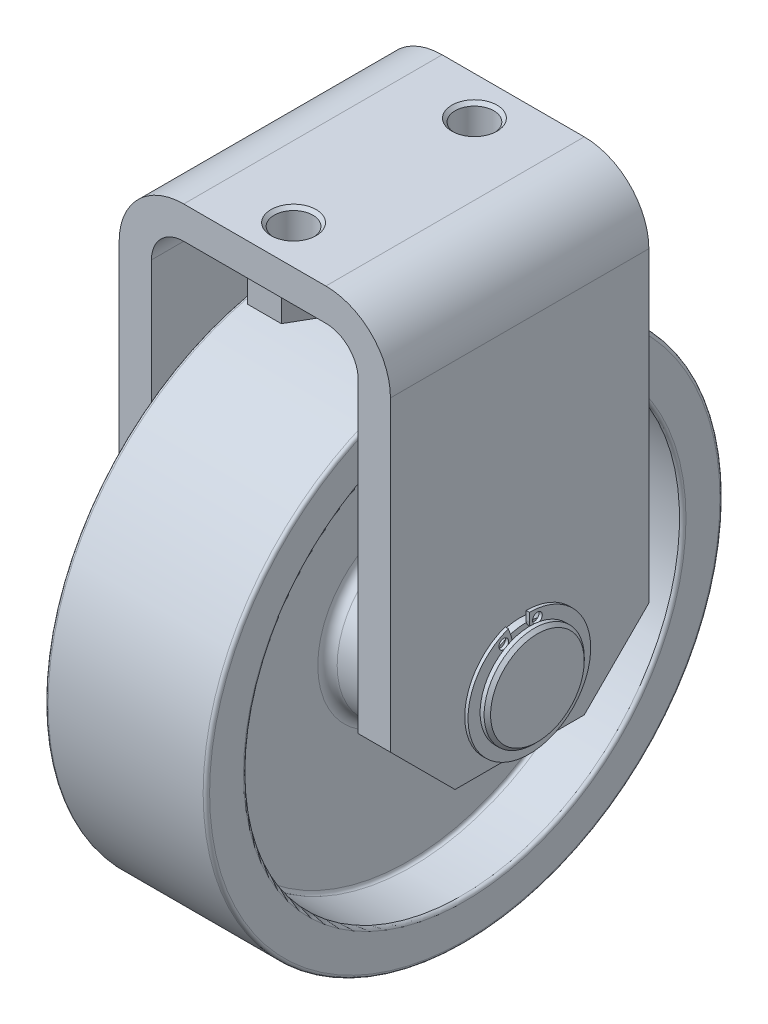
SolidWorks part; units mm, degrees
ref_plane "Front Plane" through (0, 0, 0) normal (0, 0, 1) x (1, 0, 0)
ref_plane "Top Plane" through (0, 0, 0) normal (0, 1, 0) x (1, 0, 0)
ref_plane "Right Plane" through (0, 0, 0) normal (1, 0, 0) x (0, 0, -1)
sketch "Sketch1" plane through (0, 0, 0) normal (0, 0, 1) x (1, 0, 0)
  line L0 (-43.3817, 0) -> (51.6188, 0) construction
  line L1 (55, 0) -> (-55, 0) construction
  line L2 (24, 16) -> (-24, 16)
  line L3 (0, -55) -> (0, 55) construction
  line L4 (-24, 16) -> (-24, 24)
  line L5 (-23, 25) -> (-10.5, 25)
  line L6 (-7.5, 28) -> (-7.5, 66.5)
  line L7 (-8.5, 67.5) -> (-24, 67.5)
  line L8 (-25, 68.5) -> (-25, 79)
  line L9 (-24, 80) -> (24, 80)
  line L10 (0, 80) -> (0, 16) construction
  line L11 (24, 16) -> (24, 24)
  line L12 (23, 25) -> (10.5, 25)
  line L13 (7.5, 28) -> (7.5, 66.5)
  line L14 (8.5, 67.5) -> (24, 67.5)
  line L15 (25, 68.5) -> (25, 79)
  arc A0 (-24, 24) -> (-23, 25) centre (-23, 24) cw
  arc A1 (-7.5, 66.5) -> (-8.5, 67.5) centre (-8.5, 66.5) ccw
  arc A2 (-24, 67.5) -> (-25, 68.5) centre (-24, 68.5) cw
  arc A3 (-25, 79) -> (-24, 80) centre (-24, 79) cw
  arc A4 (-10.5, 25) -> (-7.5, 28) centre (-10.5, 28) ccw
  arc A5 (24, 24) -> (23, 25) centre (23, 24) ccw
  arc A6 (10.5, 25) -> (7.5, 28) centre (10.5, 28) cw
  arc A7 (7.5, 66.5) -> (8.5, 67.5) centre (8.5, 66.5) cw
  arc A8 (24, 67.5) -> (25, 68.5) centre (24, 68.5) ccw
  arc A9 (25, 79) -> (24, 80) centre (24, 79) ccw
  point P22 (-25, 80)
  dimension "D8" = 1
  dimension "D9" = 3
  dimension "D1" = 50
  dimension "D2" = 135
  dimension "D3" = 160
  dimension "D4" = 25
  dimension "D5" = 7.5
  dimension "D6" = 24
  dimension "D7" = 16
revolve "Revolve1" add sketch "Sketch1" angle 360 about L0
sketch "Sketch2" plane through (0, 0, 0) normal (0, 0, 1) x (1, 0, 0)
  line L0 (-42, -20) -> (-42, 95)
  line L1 (-22, 115) -> (22, 115)
  line L2 (42, 95) -> (42, -20)
  line L3 (0, -88) -> (0, 88) construction
  line L4 (27.5, 0) -> (-27.5, 0) construction
  arc A0 (22, 115) -> (42, 95) centre (22, 95) cw
  arc A1 (-42, 95) -> (-22, 115) centre (-22, 95) cw
  point P2 (0, 115)
  point P11 (42, 115)
  point P14 (-42, 115)
  dimension "D4" = 20
  dimension "D1" = 135
  dimension "D2" = 84
  dimension "D3" = 115
extrude "Extrude-Thin1" add sketch "Sketch2" along normal mid plane 80 separate body thin
sketch "Sketch3" plane through (42, 0, 0) normal (1, 0, 0) x (0, 0, -1)
  circle A0 centre (0, 0) radius 16
  circle A1 centre (0, 0) radius 16 construction
extrude "Cut-Extrude1" cut sketch "Sketch3" against normal up to surface (84 mm away) up to face at (-42, 37.5, 0)
sketch "Sketch4" plane through (0, 0, 0) normal (1, 0, 0) x (0, 0, -1)
  circle A2 centre (0, 0) radius 15.5
  circle A3 centre (0, 0) radius 15.5
  dimension "D1" = 0.5
extrude "Boss-Extrude1" add sketch "Sketch4" along normal mid plane 95 separate body
chamfer "Chamfer1" distance 1 angle 45 2 edges at (-47.5, 0, -15.5) (47.5, 0, -15.5)
sketch "Sketch5" plane through (0, 0, 0) normal (0, 0, 1) x (1, 0, 0)
  line L0 (46.5, 15.5) -> (-46.5, 15.5) construction
  line L1 (-45.25, 15.5) -> (-43.75, 15.5)
  line L2 (-45.25, 15.5) -> (-45.25, 13.5)
  line L3 (-45.25, 13.5) -> (-43.75, 13.5)
  line L4 (-43.75, 15.5) -> (-43.75, 13.5)
  line L5 (-45.25, 15.5) -> (-43.75, 13.5) construction
  line L6 (-45.25, 13.5) -> (-43.75, 15.5) construction
  line L7 (-47.5, 14.5) -> (-47.5, -14.5) construction
  line L8 (0, 129.3642) -> (0, -93.634) construction
  line L9 (0, -88) -> (0, 88) construction
  line L10 (43.75, 15.5) -> (43.75, 13.5)
  line L11 (45.25, 15.5) -> (43.75, 15.5)
  line L12 (45.25, 15.5) -> (45.25, 13.5)
  line L13 (45.25, 13.5) -> (43.75, 13.5)
  point P4 (-44.5, 14.5)
  dimension "D1" = 3
  dimension "D2" = 1.5
  dimension "D3" = 2
revolve "Cut-Revolve1" cut sketch "Sketch5" angle 360
sketch "Sketch6" plane through (0, 0, 0) normal (0, 0, 1) x (1, 0, 0)
  line L0 (-43.75, 13.5) -> (-45.25, 13.5) construction
  line L1 (-45, 14) -> (-44, 14)
  line L2 (-45, 14) -> (-45, 19)
  line L3 (-45, 19) -> (-44, 19)
  line L4 (-44, 14) -> (-44, 19)
  line L5 (-45, 14) -> (-44, 19) construction
  line L6 (-45, 19) -> (-44, 14) construction
  line L7 (-45.25, -15.5) -> (-45.25, 15.5) construction
  point P4 (-44.5, 16.5)
  dimension "D1" = 5
  dimension "D2" = 0.5
  dimension "D3" = 1
  dimension "D4" = 0.25
revolve "Revolve2" add sketch "Sketch6" angle 340
sketch "Sketch7" plane through (-45, 0, 0) normal (-1, 0, 0) x (0, 0, 1)
  line L0 (0, 19) -> (0, 14) construction
  line L1 (6.4984, 17.8542) -> (4.7883, 13.1557) construction
  circle A0 centre (7.9274, 14.4709) radius 1.5
  circle A1 centre (-2.5, 16.3095) radius 1.5
  arc A4 (0, 16.5) -> (5.6433, 15.5049) centre (0, 0) ccw
  arc A5 (0, 16.5) -> (5.6433, 15.5049) centre (0, 0) ccw construction
  dimension "D1" = 2.5
  dimension "D3" = 3
  dimension "D2" = 2.5
  dimension "D4" = 2.5
extrude "Cut-Extrude2" cut sketch "Sketch7" against normal up to surface (1 mm away) up to face at (-44, -0.1234, -0.0218)
fillet "Fillet1" radius 2.5 2 edges at (-44.5, 13.1557, 4.7883) (-44.5, 14, 0)
mirror "Mirror3" about plane through (0, 0, 0) normal (1, 0, 0) of bodies 107
sketch "Sketch8" plane through (0, 105, 0) normal (0, -1, 0) x (1, 0, 0)
  line L1 (5.1962, -37) -> (10.3923, -28)
  line L2 (10.3923, -28) -> (5.1962, -19)
  line L3 (5.1962, -19) -> (-5.1962, -19)
  line L4 (-5.1962, -19) -> (-10.3923, -28)
  line L5 (-10.3923, -28) -> (-5.1962, -37)
  line L6 (-5.1962, -37) -> (5.1962, -37)
  line L7 (5.1962, -55) -> (10.3923, -46) construction
  line L8 (10.3923, -46) -> (5.1962, -37) construction
  line L9 (5.1962, -37) -> (-5.1962, -37) construction
  line L10 (-5.1962, -37) -> (-10.3923, -46) construction
  line L11 (-10.3923, -46) -> (-5.1962, -55) construction
  line L12 (-5.1962, -55) -> (5.1962, -55) construction
  circle A0 centre (0, -28) radius 9 construction
  circle A1 centre (0, -46) radius 9 construction
  circle A2 centre (0, -28) radius 6
  circle A3 centre (0, -46) radius 6 construction
  point P23 (0, -19)
  dimension "D5" = 12
  dimension "D1" = 18
  dimension "D2" = 18
  dimension "D3" = 28
extrude "Boss-Extrude2" add sketch "Sketch8" along normal blind 10
sketch "Sketch9" [suppressed] plane through (0, 0, 0) normal (1, 0, 0) x (0, 0, -1)
  line L0 (32, 70) -> (35, 70)
  line L1 (-35, 70) -> (35, 70) construction
  line L2 (35, 70) -> (35, 71.7321)
  line L3 (35, 71.7321) -> (32, 70)
  dimension "D1" = 3
  dimension "D2" = 30
revolve "Cut-Revolve2" [suppressed] cut sketch "Sketch9" angle 360
chamfer "Chamfer2" [suppressed] distance 2 angle 45
sketch "Sketch10" plane through (0, 0, 0) normal (1, 0, 0) x (0, 0, -1)
  line L0 (37, 95) -> (40, 95)
  line L1 (-40, 95) -> (40, 95) construction
  line L2 (40, 95) -> (40, 96.7321)
  line L3 (40, 96.7321) -> (37, 95)
  dimension "D1" = 30
  dimension "D2" = 3
revolve "Cut-Revolve3" cut sketch "Sketch10" angle 360 about axis through (0, 95, -28) along (0, 1, 0)
chamfer "Chamfer3" distance 2 angle 45 6 edges at (-7.7942, 105, -32.5) (-7.7942, 105, -23.5) (0, 105, -19) (0, 105, -37) (7.7942, 105, -23.5) (7.7942, 105, -32.5)
sketch "Sketch11" plane through (0, 105, 0) normal (0, -1, 0) x (1, 0, 0)
  circle A0 centre (0, -28) radius 6 construction
  circle A2 centre (0, -28) radius 6
  circle A3 centre (0, -23) radius 6 construction
extrude "Cut-Extrude3" cut sketch "Sketch11" against normal up to surface (10 mm away) up to face at (0, 115, 0)
chamfer "Chamfer4" distance 1 angle 45 1 edges at (0, 95, -34)
chamfer "Chamfer5" distance 1 angle 45 1 edges at (0, 115, -22)
sketch "Sketch12" plane through (25, 0, 0) normal (1, 0, 0) x (0, 0, -1)
  line L0 (0, -68.5) -> (0, -80) construction
  circle A0 centre (0, 0) radius 68.5 construction
  circle A1 centre (0, 0) radius 80 construction
chamfer "Chamfer6" distance 20 angle 45 4 edges at (37, -20, 40) (37, -20, -40) (-37, -20, 40) (-37, -20, -40)
mirror "Mirror4" about plane through (0, 0, 0) normal (0, 0, 1) of "Boss-Extrude2"
mirror "Mirror6" about plane through (0, 0, 0) normal (0, 0, 1) of "Cut-Extrude3"
chamfer "Chamfer7" distance 1 angle 45 2 edges at (0, 95, 34) (0, 115, 34)
